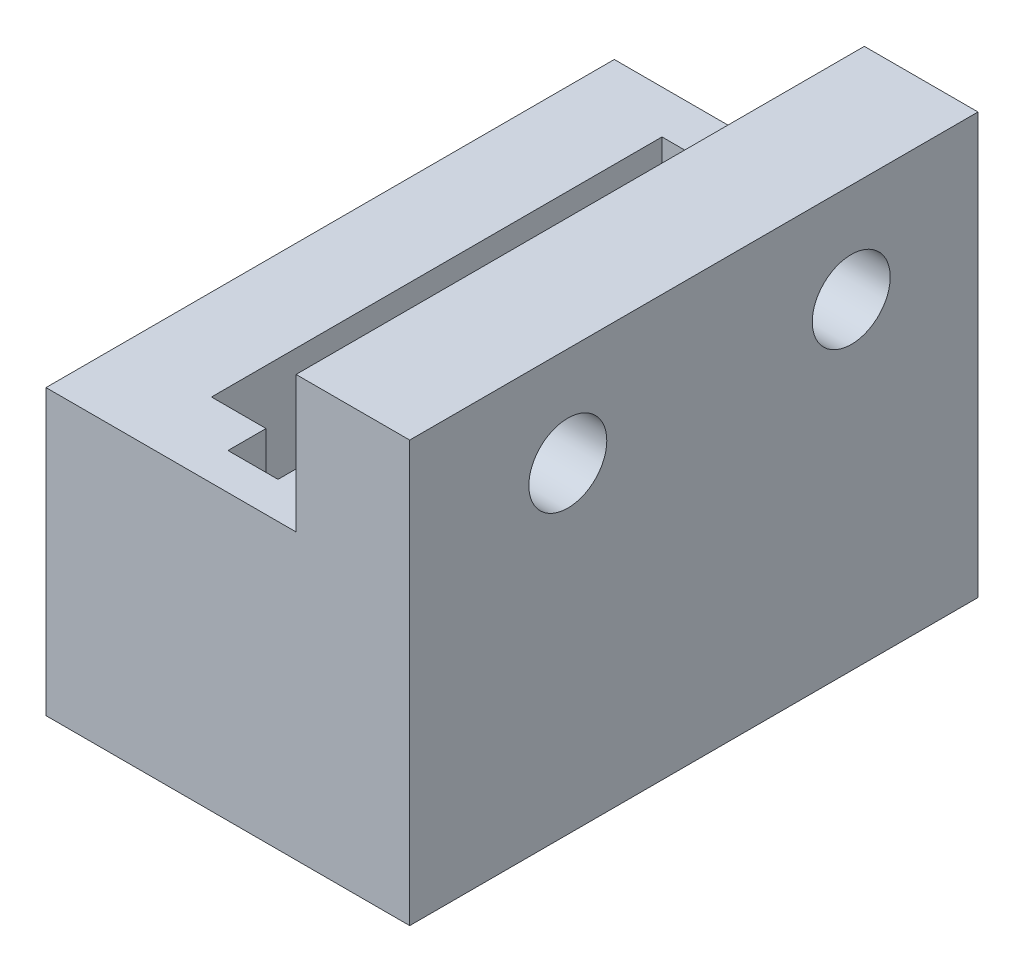
SolidWorks part; units mm, degrees
ref_plane "Front Plane" through (0, 0, 0) normal (0, 0, 1) x (1, 0, 0)
ref_plane "Top Plane" through (0, 0, 0) normal (0, 1, 0) x (1, 0, 0)
ref_plane "Right Plane" through (0, 0, 0) normal (1, 0, 0) x (0, 0, -1)
sketch "Sketch1" plane through (0, 0, 0) normal (0, 1, 0) x (1, 0, 0)
  line L1 (0, 0) -> (16, 0)
  line L2 (0, 0) -> (0, 25)
  line L3 (0, 25) -> (16, 25)
  line L4 (16, 0) -> (16, 25)
  dimension "D1" = 25
  dimension "D2" = 16
extrude "Boss-Extrude1" add sketch "Sketch1" along normal blind 12.5
sketch "Sketch2" plane through (0, 12.5, 0) normal (0, 1, 0) x (1, 0, 0)
  line L0 (16, 0) -> (16, 25) construction
  line L1 (4, 23.0983) -> (6.4, 23.0983)
  line L2 (4, 23.0983) -> (4, 3.2803)
  line L3 (4, 3.2803) -> (6.4, 3.2803)
  line L4 (11, 23.0983) -> (11, 3.2803)
  line L5 (7.5, 25) -> (7.5, 1.6053) construction
  line L6 (6.4, 23.0983) -> (6.4, 25)
  line L7 (16, 25) -> (0, 25) construction
  line L8 (6.4, 25) -> (8.6, 25)
  line L9 (8.6, 25) -> (8.6, 23.0983)
  line L10 (8.6, 23.0983) -> (11, 23.0983)
  line L11 (6.4, 3.2803) -> (6.4, 1.6053)
  line L12 (6.4, 1.6053) -> (8.6, 1.6053)
  line L13 (8.6, 1.6053) -> (8.6, 3.2803)
  line L14 (8.6, 3.2803) -> (11, 3.2803)
  dimension "D1" = 19.818
  dimension "D2" = 7
  dimension "D3" = 5
  dimension "D4" = 2.2
  dimension "D5" = 1.675
extrude "Cut-Extrude1" cut sketch "Sketch2" against normal blind 6.056
ref_plane "PLANE-CAVITY-MIDLINE" through (7.5, 0, 0) normal (1, 0, 0) x (0, 0, -1)
sketch "Sketch4" plane through (0, 12.5, 0) normal (0, 1, 0) x (1, 0, 0)
  line L0 (0, 0) -> (16, 0) construction
  line L1 (11, 0) -> (16, 0)
  line L2 (11, 0) -> (11, 25)
  line L3 (11, 25) -> (16, 25)
  line L4 (16, 0) -> (16, 25)
  line L5 (11, 3.2803) -> (11, 23.0983) construction
extrude "Boss-Extrude2" add sketch "Sketch4" along normal blind 6
sketch "Sketch3" plane through (16, 0, 0) normal (1, 0, 0) x (0, 0, -1)
  line L0 (3.2803, 6.444) -> (23.0983, 6.444) construction
  line L3 (3.2803, 6.444) -> (23.0983, 6.444) construction
  line L8 (13.1893, 6.444) -> (13.1893, -49993.556) construction
  circle A0 centre (6.9553, 14.144) radius 1.7145
  circle A1 centre (19.4233, 14.144) radius 1.7145
  circle A2 centre (6.9553, 14.144) radius 1.25 construction
  point P7 (13.1893, 6.444)
  point P8 (17.989, 14.6284)
  dimension "D1" = 3.429
  dimension "D2" = 10.7535
extrude "Cut-Extrude2" cut sketch "Sketch3" against normal up to surface (5 mm away) up to face at (11, 12.486, -12.8446)
sketch "Sketch6" plane through (0, 6.444, 0) normal (0, 1, 0) x (1, 0, 0)
  line L0 (5.875, 9.6053) -> (5.875, 3.2803) construction
  line L1 (4, 3.2803) -> (6.4, 3.2803) construction
  line L2 (9.125, 3.2803) -> (9.125, 9.6053) construction
  line L3 (8.6, 3.2803) -> (11, 3.2803) construction
  line L4 (9.125, 9.6053) -> (9.125, 17.6053) construction
  line L5 (9.125, 17.6053) -> (5.875, 17.6053) construction
  line L6 (5.875, 17.6053) -> (5.875, 9.6053) construction
  line L7 (5.875, 9.6053) -> (7.5, 9.6053) construction
  line L8 (7.5, -6.6308) -> (7.5, 6.6308) construction
  line L9 (7.5, 9.6053) -> (9.125, 9.6053) construction
  circle A0 centre (5.875, 9.6053) radius 0.5
  circle A1 centre (9.125, 9.6053) radius 0.5
  circle A2 centre (5.875, 17.6053) radius 0.5
  circle A3 centre (9.125, 17.6053) radius 0.5
  dimension "D1" = 1
  dimension "D2" = 8
  dimension "D3" = 1.625
  dimension "D4" = 6.325
extrude "Cut-Extrude3" cut sketch "Sketch6" against normal blind 4
sketch "Sketch7" plane through (0, 6.444, 0) normal (0, 1, 0) x (1, 0, 0)
  line L0 (7.5, 1.6053) -> (7.5, 5.6053) construction
  line L1 (6.4, 1.6053) -> (8.6, 1.6053) construction
  line L2 (7.5, -6.6308) -> (7.5, 6.6308) construction
  line L3 (7.5, 5.6053) -> (7.5, 13.6053) construction
  line L4 (7.5, 13.6053) -> (7.5, 21.6053) construction
  line L5 (8.6, 3.2803) -> (11, 3.2803) construction
  circle A0 centre (7.5, 21.6053) radius 1.5
  circle A1 centre (7.5, 13.6053) radius 1.5
  circle A2 centre (7.5, 5.6053) radius 1.5
  dimension "D2" = 8
  dimension "D3" = 8
  dimension "D1" = 2.325
  dimension "D4" = 3
extrude "Cut-Extrude4" cut sketch "Sketch7" against normal blind 2
